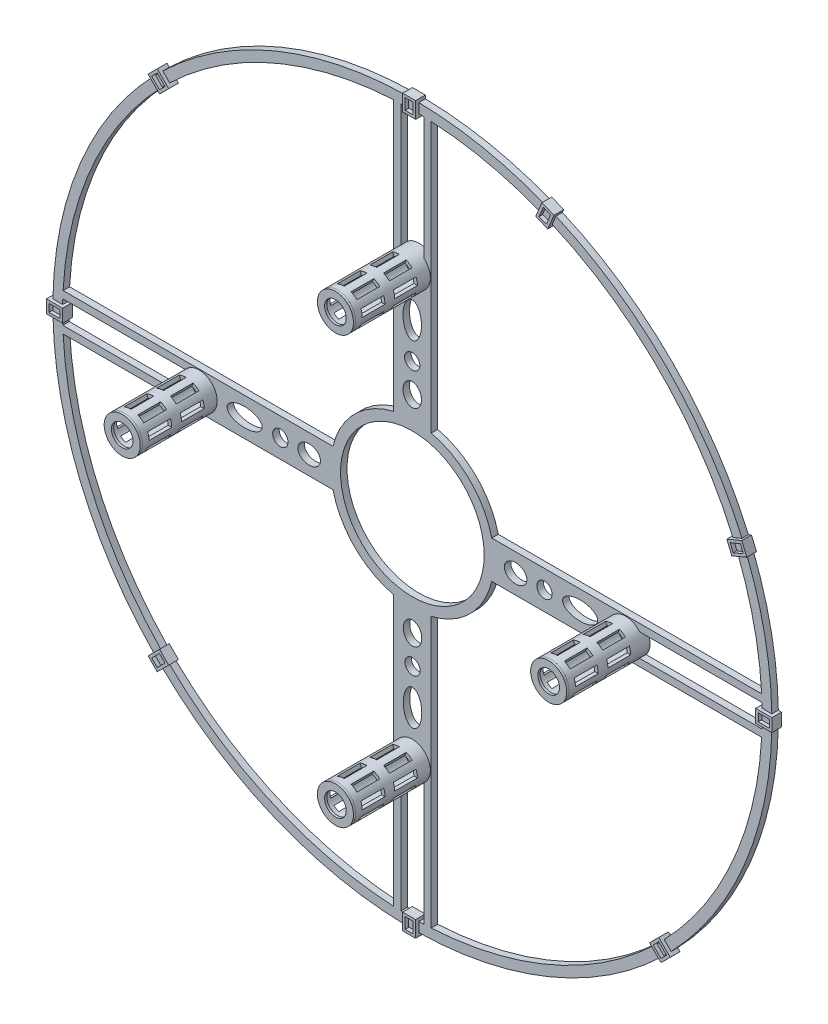
SolidWorks part; units mm, degrees
material "PLA"
ref_plane "Front Plane" through (0, 0, 0) normal (0, 0, 1) x (1, 0, 0)
ref_plane "Top Plane" through (0, 0, 0) normal (0, 1, 0) x (1, 0, 0)
ref_plane "Right Plane" through (0, 0, 0) normal (1, 0, 0) x (0, 0, -1)
sketch "Sketch1" plane through (0, 0, 0) normal (0, 0, 1) x (1, 0, 0)
  line L0 (5.7854, 24.4498) -> (5.7854, 107.5764)
  line L1 (-5.7854, 24.4498) -> (-5.7854, 107.5764)
  line L2 (3.5358, 69.9509) -> (3.5358, 107.6738)
  line L3 (-3.5358, 69.9526) -> (-3.5358, 107.6738)
  line L4 (69.9509, -3.5358) -> (107.6738, -3.5358)
  line L5 (69.9526, 3.5358) -> (107.6738, 3.5358)
  line L6 (24.4498, 5.7854) -> (107.5764, 5.7854)
  line L7 (24.4498, -5.7854) -> (107.5764, -5.7854)
  line L8 (-3.5358, -69.9509) -> (-3.5358, -107.6738)
  line L9 (3.5358, -69.9526) -> (3.5358, -107.6738)
  line L10 (5.7854, -24.4498) -> (5.7854, -107.5764)
  line L11 (-5.7854, -24.4498) -> (-5.7854, -107.5764)
  line L12 (-69.9509, 3.5358) -> (-107.6738, 3.5358)
  line L13 (-69.9526, -3.5358) -> (-107.6738, -3.5358)
  line L14 (-24.4498, -5.7854) -> (-107.5764, -5.7854)
  line L15 (-24.4498, 5.7854) -> (-107.5764, 5.7854)
  circle A0 centre (0, 0) radius 22.125
  circle A1 centre (0, 0) radius 25.125
  circle A3 centre (0, 0) radius 107.7318
  circle A4 centre (0, 65.6738) radius 3.3306
  circle A5 centre (0, 65.6738) radius 4.45
  circle A6 centre (0, 65.6738) radius 5.5557
  circle A7 centre (-0.0492, 40.6702) radius 2.35
  circle A10 centre (65.6738, 0) radius 5.5557
  circle A11 centre (65.6738, 0) radius 4.45
  circle A12 centre (65.6738, 0) radius 3.3306
  circle A13 centre (40.6702, 0.0492) radius 2.35
  circle A14 centre (0, -65.6738) radius 5.5557
  circle A15 centre (0, -65.6738) radius 4.45
  circle A16 centre (0, -65.6738) radius 3.3306
  circle A17 centre (0.0492, -40.6702) radius 2.35
  circle A18 centre (-65.6738, 0) radius 5.5557
  circle A19 centre (-65.6738, 0) radius 4.45
  circle A20 centre (-65.6738, 0) radius 3.3306
  circle A21 centre (-40.6702, -0.0492) radius 2.35
  circle A22 centre (0, 0) radius 110.7318
  circle A23 centre (0, 65.6738) radius 37.5 construction
  arc A24 (-5.7854, 65.4184) -> (-65.4184, 5.7854) centre (0, 0) ccw construction
  ellipse E0 centre (-0.0492, 51.6644) end of major axis (-0.0492, 57.0732) minor radius 2.8411
  ellipse E1 centre (-0.0492, 31.7853) end of major axis (-0.0492, 35.2645) minor radius 2.8411
  ellipse E2 centre (51.6644, 0.0492) end of major axis (57.0732, 0.0492) minor radius 2.8411
  ellipse E3 centre (31.7853, 0.0492) end of major axis (28.3061, 0.0492) minor radius 2.8411
  ellipse E4 centre (0.0492, -51.6644) end of major axis (0.0492, -46.2556) minor radius 2.8411
  ellipse E5 centre (0.0492, -31.7853) end of major axis (0.0492, -35.2645) minor radius 2.8411
  ellipse E6 centre (-51.6644, -0.0492) end of major axis (-57.0732, -0.0492) minor radius 2.8411
  ellipse E7 centre (-31.7853, -0.0492) end of major axis (-35.2645, -0.0492) minor radius 2.8411
  point P76 (0, 0)
  point P93 (0, 0)
  point P118 (0, 0)
  dimension "D1" = 44.25
  dimension "D2" = 4
  dimension "D5" = 3
  dimension "D3" = 65.6738
  dimension "D4" = 42
  dimension "D8" = 65.6738
  dimension "D9" = 11.1113
  dimension "D10" = 8.9
  dimension "D11" = 6.6613
  dimension "D18" = 4.7
  dimension "D20" = 28.3061
  dimension "D26" = 24.4498
  dimension "D31" = 4.7
  dimension "D33" = 75
  dimension "D12" = 19.8791
  dimension "D13" = 31.7853
  dimension "D14" = 6.9584
  dimension "D15" = 5.6822
  dimension "D16" = 8.8849
  dimension "D17" = 10.9943
  dimension "D19" = 40.6702
  dimension "D21" = 46.2556
  dimension "D22" = 10.8176
  dimension "D23" = 5.6822
  dimension "D24" = 5.8346
  dimension "D25" = 5.7362
  dimension "D27" = 24.4498
  dimension "D28" = 5.7854
  dimension "D29" = 2.2496
  dimension "D30" = 2.2496
  dimension "D32" = 40.6702
  dimension "D7" = 3
  dimension "D6" = 4
extrude "Boss-Extrude1" add sketch "Sketch1" along normal blind 2 separate body contours A22 A3 | A14 L9 A3 L10 A1 L11 L8 E5 E4 A17 | A10 L5 A3 L6 A1 L7 L4 E3 E2 A13 | A1 A0 | A6 L3 A3 L1 A1 L0 L2 E1 E0 A7 | A18 L13 A3 L14 A1 L15 L12 E7 E6 A21 | A14 A15 | A10 A11 | A18 A19 | A6 A5 region at (0.0095, 58.9166, 0) region at (17.2636, 17.2636, 0) region at (58.9166, -0.0095, 0) region at (-58.9166, 0.0095, 0) region at (4.8833, 67.9755, 0) region at (70.7543, 1.8254, 0) region at (-0.0095, -58.9166, 0) region at (-63.8484, 5.0806, 0) region at (0, -71.0723, 0) region at (-110.4186, 0, 0)
extrude "Boss-Extrude2" add sketch "Sketch1<5>" along normal blind 25 contours A6 A5 | A10 A11 | A14 A15 | A18 A19 region at (4.8833, 67.9755, 0) region at (70.7543, 1.8254, 0) region at (-63.8484, 5.0806, 0) region at (0, -71.0723, 0)
sketch "Sketch1<5>" plane through (0, 0, 0) normal (0, 0, 1) x (1, 0, 0) same geometry as "Sketch1"
sketch "Sketch3" plane through (0, 0, 0) normal (0, 0, 1) x (1, 0, 0)
  line L0 (1.2, 107.5251) -> (1.2, 110.9253)
  line L3 (-1.2, 107.5251) -> (-1.2, 110.9253)
  line L4 (1, 107.7272) -> (1, 110.7273)
  line L5 (-1, 107.7272) -> (-1, 110.7273)
  line L8 (107.7272, 1) -> (110.7273, 1)
  line L9 (107.7272, -1) -> (110.7273, -1)
  line L10 (76.8817, -75.4675) -> (79.0031, -77.5889)
  line L11 (75.4675, -76.8817) -> (77.5889, -79.0031)
  line L12 (1, -107.7272) -> (1, -110.7273)
  line L13 (-1, -107.7272) -> (-1, -110.7273)
  line L14 (-75.4675, -76.8817) -> (-77.5889, -79.0031)
  line L15 (-76.8817, -75.4675) -> (-79.0031, -77.5889)
  line L16 (-107.7272, -1) -> (-110.7273, -1)
  line L17 (-107.7272, 1) -> (-110.7273, 1)
  line L18 (-76.8817, 75.4675) -> (-79.0031, 77.5889)
  line L19 (-75.4675, 76.8817) -> (-77.5889, 79.0031)
  line L20 (75.4675, 76.8817) -> (77.5889, 79.0031) [skipped]
  line L21 (76.8817, 75.4675) -> (79.0031, 77.5889) [skipped]
  line L22 (0, 0) -> (76.1779, 76.1779) construction
  line L23 (0, 0) -> (99.5312, 41.2272) construction
  line L24 (0, 0) -> (119.7649, 0) construction
  line L25 (0, 0) -> (105.6618, 21.0174) construction
  line L26 (99.1442, 42.1493) -> (101.916, 43.2974)
  line L27 (99.9096, 40.3015) -> (102.6814, 41.4496)
  line L28 (0, 0) -> (41.2272, 99.5312) construction
  line L29 (40.3015, 99.9096) -> (41.4496, 102.6814)
  line L30 (42.1493, 99.1442) -> (43.2974, 101.916)
  line L31 (2, 106.7131) -> (2, 111.7139)
  line L32 (-2, 106.7131) -> (-2, 111.7139)
  line L35 (106.7131, -2) -> (111.7139, -2)
  line L36 (106.7131, 2) -> (111.7139, 2)
  line L37 (74.0433, -76.8717) -> (77.5794, -80.4079)
  line L38 (76.8717, -74.0433) -> (80.4079, -77.5794)
  line L39 (-2, -106.7131) -> (-2, -111.7139)
  line L40 (2, -106.7131) -> (2, -111.7139)
  line L41 (-76.8717, -74.0433) -> (-80.4079, -77.5794)
  line L42 (-74.0433, -76.8717) -> (-77.5794, -80.4079)
  line L43 (-106.7131, 2) -> (-111.7139, 2)
  line L44 (-106.7131, -2) -> (-111.7139, -2)
  line L45 (-74.0433, 76.8717) -> (-77.5794, 80.4079)
  line L46 (-76.8717, 74.0433) -> (-80.4079, 77.5794)
  line L47 (76.8717, 74.0433) -> (80.4079, 77.5794) [skipped]
  line L48 (74.0433, 76.8717) -> (77.5794, 80.4079) [skipped]
  line L49 (99.3554, 38.9896) -> (103.9756, 40.9033)
  line L50 (97.8247, 42.6851) -> (102.4448, 44.5988)
  line L51 (42.6851, 97.8247) -> (44.5988, 102.4448)
  line L52 (38.9896, 99.3554) -> (40.9033, 103.9756)
  line L53 (0, 106.2791) -> (0, 112.1248) construction
  line L56 (107.5251, -1.2) -> (110.9253, -1.2)
  line L57 (107.5251, 1.2) -> (110.9253, 1.2)
  line L58 (75.1832, -76.8803) -> (77.5875, -79.2846)
  line L59 (76.8803, -75.1832) -> (79.2846, -77.5875)
  line L60 (-1.2, -107.5251) -> (-1.2, -110.9253)
  line L61 (1.2, -107.5251) -> (1.2, -110.9253)
  line L62 (-76.8803, -75.1832) -> (-79.2846, -77.5875)
  line L63 (-75.1832, -76.8803) -> (-77.5875, -79.2846)
  line L64 (-107.5251, 1.2) -> (-110.9253, 1.2)
  line L65 (-107.5251, -1.2) -> (-110.9253, -1.2)
  line L66 (-75.1832, 76.8803) -> (-77.5875, 79.2846)
  line L67 (-76.8803, 75.1832) -> (-79.2846, 77.5875)
  line L68 (99.7995, 40.0394) -> (102.9408, 41.3406)
  line L69 (98.881, 42.2567) -> (102.0224, 43.5579)
  line L70 (42.2567, 98.881) -> (43.5579, 102.0224)
  line L71 (40.0394, 99.7995) -> (41.3406, 102.9408)
  circle A3 centre (0, 0) radius 110.7318 construction
  arc A4 (1, 110.7273) -> (-1, 110.7273) centre (0, 0) ccw
  circle A5 centre (0, 0) radius 107.7318 construction
  arc A6 (1, 107.7272) -> (-1, 107.7272) centre (0, 0) ccw
  arc A7 (110.7273, -1) -> (110.7273, 1) centre (0, 0) ccw
  arc A8 (107.7272, -1) -> (107.7272, 1) centre (0, 0) ccw
  arc A9 (77.5889, -79.0031) -> (79.0031, -77.5889) centre (0, 0) ccw
  arc A10 (75.4675, -76.8817) -> (76.8817, -75.4675) centre (0, 0) ccw
  arc A11 (-1, -110.7273) -> (1, -110.7273) centre (0, 0) ccw
  arc A12 (-1, -107.7272) -> (1, -107.7272) centre (0, 0) ccw
  arc A13 (-79.0031, -77.5889) -> (-77.5889, -79.0031) centre (0, 0) ccw
  arc A14 (-76.8817, -75.4675) -> (-75.4675, -76.8817) centre (0, 0) ccw
  arc A15 (-110.7273, 1) -> (-110.7273, -1) centre (0, 0) ccw
  arc A16 (-107.7272, 1) -> (-107.7272, -1) centre (0, 0) ccw
  arc A17 (-77.5889, 79.0031) -> (-79.0031, 77.5889) centre (0, 0) ccw
  arc A18 (-75.4675, 76.8817) -> (-76.8817, 75.4675) centre (0, 0) ccw
  arc A19 (79.0031, 77.5889) -> (77.5889, 79.0031) centre (0, 0) ccw [skipped]
  arc A20 (76.8817, 75.4675) -> (75.4675, 76.8817) centre (0, 0) ccw [skipped]
  arc A21 (107.5764, 5.7854) -> (5.7854, 107.5764) centre (0, 0) ccw construction
  arc A22 (99.1442, 42.1493) -> (99.9096, 40.3015) centre (0, 0) cw
  arc A23 (101.916, 43.2974) -> (102.6814, 41.4496) centre (0, 0) cw
  arc A24 (43.2974, 101.916) -> (41.4496, 102.6814) centre (0, 0) ccw
  arc A25 (42.1493, 99.1442) -> (40.3015, 99.9096) centre (0, 0) ccw
  arc A26 (2, 111.7139) -> (-2, 111.7139) centre (0, 0) ccw
  arc A27 (2, 106.7131) -> (-2, 106.7131) centre (0, 0) ccw
  arc A30 (111.7139, -2) -> (111.7139, 2) centre (0, 0) ccw
  arc A31 (106.7131, -2) -> (106.7131, 2) centre (0, 0) ccw
  arc A32 (77.5794, -80.4079) -> (80.4079, -77.5794) centre (0, 0) ccw
  arc A33 (74.0433, -76.8717) -> (76.8717, -74.0433) centre (0, 0) ccw
  arc A34 (-2, -111.7139) -> (2, -111.7139) centre (0, 0) ccw
  arc A35 (-2, -106.7131) -> (2, -106.7131) centre (0, 0) ccw
  arc A36 (-80.4079, -77.5794) -> (-77.5794, -80.4079) centre (0, 0) ccw
  arc A37 (-76.8717, -74.0433) -> (-74.0433, -76.8717) centre (0, 0) ccw
  arc A38 (-111.7139, 2) -> (-111.7139, -2) centre (0, 0) ccw
  arc A39 (-106.7131, 2) -> (-106.7131, -2) centre (0, 0) ccw
  arc A40 (-77.5794, 80.4079) -> (-80.4079, 77.5794) centre (0, 0) ccw
  arc A41 (-74.0433, 76.8717) -> (-76.8717, 74.0433) centre (0, 0) ccw
  arc A42 (80.4079, 77.5794) -> (77.5794, 80.4079) centre (0, 0) ccw [skipped]
  arc A43 (76.8717, 74.0433) -> (74.0433, 76.8717) centre (0, 0) ccw [skipped]
  arc A44 (97.8247, 42.6851) -> (99.3554, 38.9896) centre (0, 0) cw
  arc A45 (102.4448, 44.5988) -> (103.9756, 40.9033) centre (0, 0) cw
  arc A46 (44.5988, 102.4448) -> (40.9033, 103.9756) centre (0, 0) ccw
  arc A47 (42.6851, 97.8247) -> (38.9896, 99.3554) centre (0, 0) ccw
  arc A48 (1.2, 110.9253) -> (-1.2, 110.9253) centre (0, 0) ccw
  arc A49 (1.2, 107.5251) -> (-1.2, 107.5251) centre (0, 0) ccw
  arc A52 (110.9253, -1.2) -> (110.9253, 1.2) centre (0, 0) ccw
  arc A53 (107.5251, -1.2) -> (107.5251, 1.2) centre (0, 0) ccw
  arc A54 (77.5875, -79.2846) -> (79.2846, -77.5875) centre (0, 0) ccw
  arc A55 (75.1832, -76.8803) -> (76.8803, -75.1832) centre (0, 0) ccw
  arc A56 (-1.2, -110.9253) -> (1.2, -110.9253) centre (0, 0) ccw
  arc A57 (-1.2, -107.5251) -> (1.2, -107.5251) centre (0, 0) ccw
  arc A58 (-79.2846, -77.5875) -> (-77.5875, -79.2846) centre (0, 0) ccw
  arc A59 (-76.8803, -75.1832) -> (-75.1832, -76.8803) centre (0, 0) ccw
  arc A60 (-110.9253, 1.2) -> (-110.9253, -1.2) centre (0, 0) ccw
  arc A61 (-107.5251, 1.2) -> (-107.5251, -1.2) centre (0, 0) ccw
  arc A62 (-77.5875, 79.2846) -> (-79.2846, 77.5875) centre (0, 0) ccw
  arc A63 (-75.1832, 76.8803) -> (-76.8803, 75.1832) centre (0, 0) ccw
  arc A64 (98.881, 42.2567) -> (99.7995, 40.0394) centre (0, 0) cw
  arc A65 (102.0224, 43.5579) -> (102.9408, 41.3406) centre (0, 0) cw
  arc A66 (42.2567, 98.881) -> (40.0394, 99.7995) centre (0, 0) ccw
  arc A67 (43.5579, 102.0224) -> (41.3406, 102.9408) centre (0, 0) ccw
  point P2 (1, 114.3965)
  point P42 (0, 0)
  point P99 (0, 0)
  point P145 (0, 0)
  dimension "D1" = 2
  dimension "D3" = 22.5
  dimension "D4" = 11.25
  dimension "D5" = 45
  dimension "D6" = 1
  dimension "D8" = 0.2
  dimension "D2" = 8
  dimension "D7" = 8
extrude "Boss-Extrude3" add sketch "Sketch3" along normal blind 3 contours A41 L45 A40 L46 L66 A63 L67 A62 | A27 L31 A26 L32 L0 A49 L3 A48 | A47 L51 A46 L52 A67 L70 A66 L71 | A45 L50 A44 L49 L69 A65 L68 A64 | A31 L35 A30 L36 L56 A53 L57 A52 | A33 L37 A32 L38 L58 A55 L59 A54 | A35 L39 A34 L40 L60 A57 L61 A56 | A37 L41 A36 L42 L62 A59 L63 A58 | A39 L43 A38 L44 L64 A61 L65 A60 region at (0, 106.796, 0) region at (106.796, 0, 0) region at (75.5344, -75.5344, 0) region at (0, -106.796, 0) region at (-75.5344, -75.5344, 0) region at (-106.796, 0, 0) region at (-75.5344, 75.5344, 0) region at (98.6842, 40.8764, 0) region at (40.8764, 98.6842, 0)
extrude "Boss-Extrude4" add sketch "Sketch1<6>" along normal blind 0.7 from surface separate body contours A5 A4 | A6 A5 | A10 A11 | A11 A12 | A14 A15 | A15 A16 | A18 A19 | A19 A20 region at (4.8833, 67.9755, 0) region at (70.7543, 1.8254, 0) region at (-63.8484, 5.0806, 0) region at (0, -71.0723, 0) region at (-4.3241, 65.6738, 0) region at (61.3496, 0, 0) region at (-4.3241, -65.6738, 0) region at (-69.9979, 0, 0) starting at face at (5.5557, 65.6738, 25)
sketch "Sketch1<6>" plane through (0, 0, 0) normal (0, 0, 1) x (1, 0, 0) same geometry as "Sketch1"
sketch "Sketch4" plane through (0, 0, 0) normal (0, 0, 1) x (1, 0, 0)
  line L0 (0, 70.1238) -> (0, 71.2294)
  line L1 (1.7029, 69.785) -> (2.1261, 70.8065)
  line L2 (3.1466, 68.8204) -> (3.9285, 69.6022)
  line L3 (4.1113, 67.3767) -> (5.1328, 67.7998)
  line L4 (4.45, 65.6738) -> (5.5557, 65.6738)
  line L5 (4.1113, 63.9708) -> (5.1328, 63.5477)
  line L6 (3.1466, 62.5271) -> (3.9285, 61.7453)
  line L7 (1.7029, 61.5625) -> (2.1261, 60.541)
  line L8 (0, 61.2238) -> (0, 60.1181)
  line L9 (-1.7029, 61.5625) -> (-2.1261, 60.541)
  line L10 (-3.1466, 62.5271) -> (-3.9285, 61.7453)
  line L11 (-4.1113, 63.9708) -> (-5.1328, 63.5477)
  line L12 (-4.45, 65.6738) -> (-5.5557, 65.6738)
  line L13 (-4.1113, 67.3767) -> (-5.1328, 67.7998)
  line L14 (-3.1466, 68.8204) -> (-3.9285, 69.6022)
  line L15 (-1.7029, 69.785) -> (-2.1261, 70.8065)
  circle A0 centre (0, 65.6738) radius 4.45 construction
  circle A1 centre (0, 65.6738) radius 4.45
  circle A2 centre (0, 65.6738) radius 5.5557 construction
  circle A3 centre (0, 65.6738) radius 5.5557
  circle A4 centre (0, 65.6738) radius 5.5557
extrude "Cut-Extrude1" cut sketch "Sketch4" along normal blind 7 from offset 6 contours L8 A3 L7 A1 | L6 A3 L5 A1 | L4 A3 L3 A1 | L2 A3 L1 A1 | L0 A3 L15 A1 | L14 A3 L13 A1 | L12 A3 L11 A1 | L10 A3 L9 A1 region at (-0.9737, 70.5689, 0) region at (2.7728, 69.8236, 0) region at (-4.1499, 68.4466, 0) region at (4.8951, 66.6475, 0) region at (-4.8951, 64.7001, 0) region at (4.1499, 62.9009, 0) region at (-2.7728, 61.5239, 0) region at (0.9737, 60.7787, 0)
extrude "Cut-Extrude2" cut sketch "Sketch4<4>" against normal blind 7 from offset 23 contours L8 A3 L7 A1 | L6 A3 L5 A1 | L4 A3 L3 A1 | L2 A3 L1 A1 | L0 A3 L15 A1 | L14 A3 L13 A1 | L12 A3 L11 A1 | L10 A3 L9 A1 region at (-0.9737, 70.5689, 0) region at (2.7728, 69.8236, 0) region at (-4.1499, 68.4466, 0) region at (4.8951, 66.6475, 0) region at (-4.8951, 64.7001, 0) region at (4.1499, 62.9009, 0) region at (-2.7728, 61.5239, 0) region at (0.9737, 60.7787, 0)
sketch "Sketch4<4>" plane through (0, 0, 0) normal (0, 0, 1) x (1, 0, 0) same geometry as "Sketch4"
pattern_circular "CirPattern1" count 4 over 360 about axis through (0, 0, 2) along (0, 0, -1) of "Cut-Extrude2", "Cut-Extrude1"
